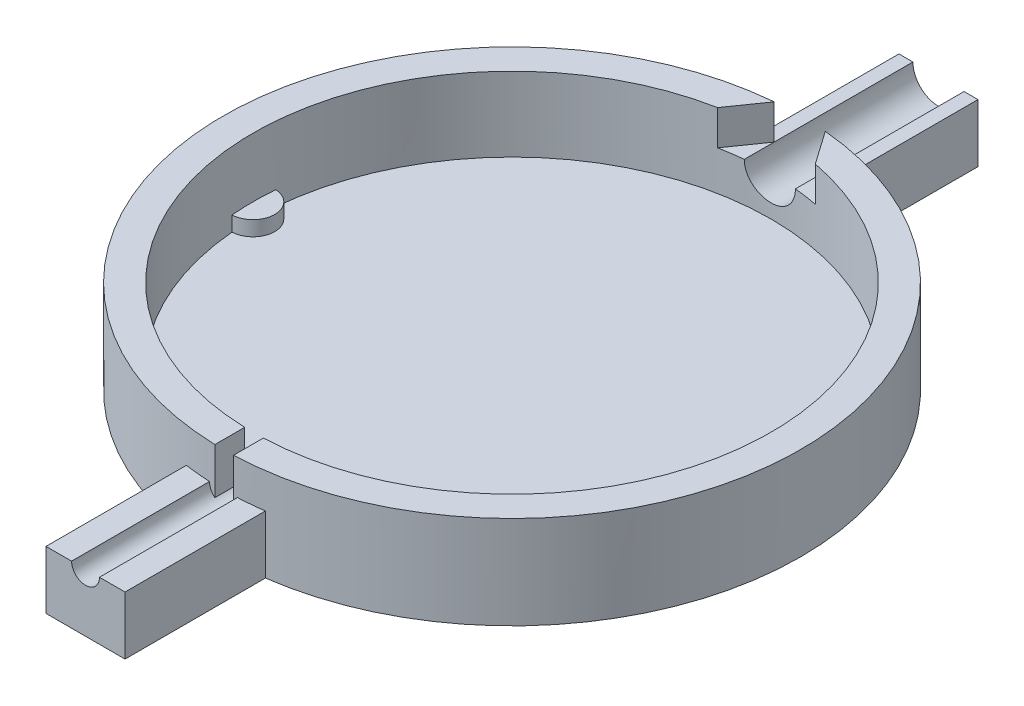
SolidWorks part; units mm, degrees
ref_plane "Front Plane" through (0, 0, 0) normal (0, 0, 1) x (1, 0, 0)
ref_plane "Top Plane" through (0, 0, 0) normal (0, 1, 0) x (1, 0, 0)
ref_plane "Right Plane" through (0, 0, 0) normal (1, 0, 0) x (0, 0, -1)
sketch "Sketch1" plane through (0, 0, 0) normal (0, 1, 0) x (1, 0, 0)
  circle A0 centre (0, 0) radius 31.06
  dimension "D1" = 62.12
extrude "Boss-Extrude1" add sketch "Sketch1" along normal blind 10
sketch "Sketch2" plane through (0, 10, 0) normal (0, 1, 0) x (1, 0, 0)
  circle A0 centre (0, 0) radius 27.86
  circle A1 centre (0, 0) radius 31.06 construction
  circle A2 centre (0, 0) radius 31.06
  dimension "D1" = 3.2
extrude "Cut-Extrude1" cut sketch "Sketch2" against normal blind 8 contours A0 region at (0, 10, 0)
sketch "Sketch3" plane through (0, 2, 0) normal (0, 1, 0) x (1, 0, 0)
  arc A0 (-27.7609, -2.3479) -> (-27.7609, 2.3479) centre (-27.86, 0) ccw
  circle A1 centre (0, 0) radius 27.86 construction
  arc A2 (27.7609, 2.3479) -> (27.7609, -2.3479) centre (27.86, 0) ccw
  arc A3 (27.7609, -2.3479) -> (27.7609, 2.3479) centre (0, 0) ccw
  arc A4 (-27.7609, 2.3479) -> (-27.7609, -2.3479) centre (0, 0) ccw
  dimension "D1" = 4.7
  dimension "D2" = 4.7
extrude "Boss-Extrude2" add sketch "Sketch3" along normal blind 1.6
sketch "Sketch4" plane through (0, 0, 0) normal (0, 0, 1) x (1, 0, 0)
  line L0 (27.7609, 2) -> (-27.7609, 2) construction
  line L1 (27.7609, 2) -> (-27.7609, 2)
  line L2 (0, 0) -> (0, 4.7714)
  line L3 (27.86, 10) -> (-27.86, 10) construction
  line L4 (27.86, 10) -> (-27.86, 10)
  line L5 (-2.75, 6.25) -> (-2.75, 10)
  line L6 (2.75, 6.25) -> (2.75, 10)
  circle A0 centre (0, 6.25) radius 2.75
  dimension "D1" = 5.5
  dimension "D2" = 4.25
extrude "Cut-Extrude2" cut sketch "Sketch4" against normal through all contours A0 L6 L4 L5 | A0 region at (0, 9.0865, 0)
sketch "Sketch5" plane through (0, 0, 0) normal (0, 0, 1) x (1, 0, 0)
  line L0 (27.86, 10) -> (-27.86, 10) construction
  line L1 (1.0982, 3.999) -> (-0.9018, 3.999)
  line L2 (1.0982, 3.999) -> (1.0982, 10)
  line L3 (1.0982, 5.999) -> (-0.9018, 5.999)
  line L4 (-0.9018, 3.999) -> (-0.9018, 10)
  line L5 (1.0982, 3.999) -> (-0.9018, 5.999) construction
  line L6 (1.0982, 5.999) -> (-0.9018, 3.999) construction
  line L7 (1.0982, 10) -> (-0.9018, 10)
  point P0 (0.0982, 4.999)
  dimension "D1" = 2
  dimension "D2" = 2
  dimension "D3" = 5
extrude "Cut-Extrude3" cut sketch "Sketch5" along normal through all contours L2 L7 L4 L1
ref_plane "Plane1" through (0, 0, -27.86) normal (0, 0, 1) x (1, 0, 0)
sketch "Sketch6" plane through (0, 0, -27.86) normal (0, 0, 1) x (1, 0, 0)
  line L0 (-31.06, 0) -> (31.06, 0) construction
  line L1 (-4.25, 0) -> (4.25, 0)
  line L2 (4.25, 6.25) -> (4.25, 0)
  line L3 (-4.25, 6.25) -> (-4.25, 0)
  line L4 (-4.25, 6.25) -> (-2.75, 6.25)
  line L5 (-2.75, 6.25) -> (-2.7454, 6.232)
  line L6 (2.75, 6.25) -> (4.25, 6.25)
  arc A0 (-2.75, 6.25) -> (2.75, 6.25) centre (0, 6.25) ccw construction
  arc A1 (-2.75, 6.25) -> (2.75, 6.25) centre (0, 6.25) ccw
extrude "Boss-Extrude3" add sketch "Sketch6" against normal blind 18 contours A1 L6 L2 L1 L3 L4
ref_plane "Plane2" through (0, 0, 27.86) normal (0, 0, -1) x (-1, 0, 0)
sketch "Sketch7" plane through (0, 0, 27.86) normal (0, 0, -1) x (-1, 0, 0)
  line L5 (4.25, 6.25) -> (2.75, 6.25)
  line L6 (-2.75, 6.25) -> (-4.25, 6.25)
  line L7 (-4.25, 6.25) -> (-4.25, 0)
  line L8 (-4.25, 0) -> (4.25, 0)
  line L9 (4.25, 0) -> (4.25, 6.25)
  line L10 (4.25, 6.25) -> (1.5, 6.25)
  line L11 (-1.5, 6.25) -> (-4.25, 6.25)
  line L12 (-4.25, 6.25) -> (-4.25, 0)
  line L13 (-4.25, 0) -> (4.25, 0)
  line L14 (4.25, 0) -> (4.25, 6.25)
  arc A0 (-1.5, 6.25) -> (1.5, 6.25) centre (0, 6.25) ccw
  arc A1 (-2.75, 6.25) -> (2.75, 6.25) centre (0, 6.25) ccw
  dimension "D2" = 3
  dimension "D1" = 0
extrude "Boss-Extrude4" add sketch "Sketch7" against normal blind 18
sketch "Sketch8" plane through (0, 10, 0) normal (0, 1, 0) x (1, 0, 0)
  line L0 (2.75, 27.7239) -> (2.75, 30.938) construction
  line L1 (-2.75, 27.7239) -> (-2.75, 30.938) construction
  line L2 (2.75, 27.7239) -> (2.75, 30.938)
  line L3 (-2.75, 27.7239) -> (-2.75, 30.938)
  line L4 (-2.75, 30.938) -> (-5.2555, 27.3598)
  line L5 (2.75, 30.938) -> (5.2555, 27.3598)
  arc A0 (-2.75, 27.7239) -> (-0.9018, -27.8454) centre (0, 0) ccw construction
  arc A1 (1.0982, -27.8383) -> (2.75, 27.7239) centre (0, 0) ccw construction
  arc A2 (-2.75, 27.7239) -> (-5.2555, 27.3598) centre (0, 0) ccw
  arc A3 (5.2555, 27.3598) -> (2.75, 27.7239) centre (0, 0) ccw
  dimension "D1" = 35
  dimension "D2" = 35
extrude "Cut-Extrude4" cut sketch "Sketch8" against normal up to surface (3.75 mm away) up to face at (3.5003, 6.25, -38.3587)
